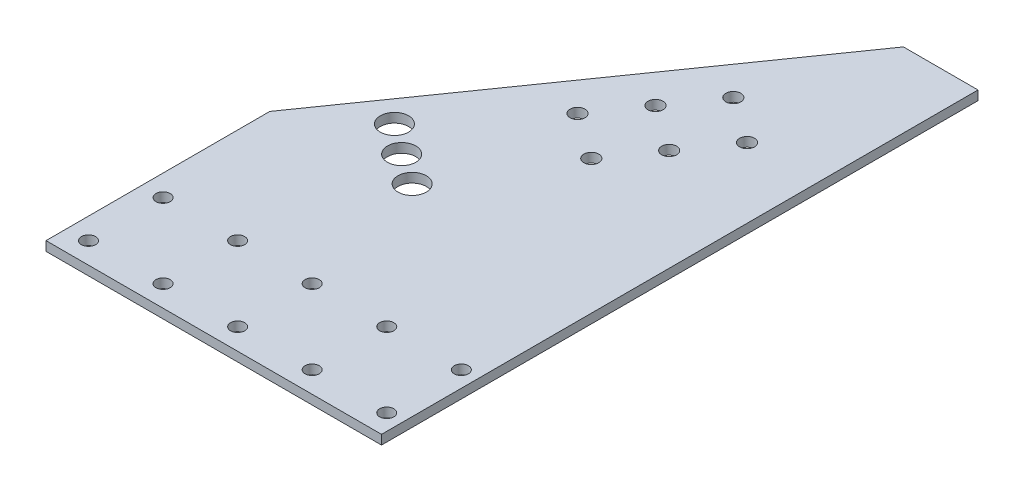
SolidWorks part; units mm, degrees
material "6061-T6 (SS)"
ref_plane "Front Plane" through (0, 0, 0) normal (0, 0, 1) x (1, 0, 0)
ref_plane "Top Plane" through (0, 0, 0) normal (0, 1, 0) x (1, 0, 0)
ref_plane "Right Plane" through (0, 0, 0) normal (1, 0, 0) x (0, 0, -1)
sketch "Sketch1" plane through (0, 0, 0) normal (0, 1, 0) x (1, 0, 0)
  line L5 (0, 0) -> (114.3, 0)
  line L6 (0, 0) -> (0, 203.2)
  line L7 (0, 203.2) -> (114.3, 203.2)
  line L8 (114.3, 0) -> (114.3, 203.2)
  dimension "D1" = 203.2
  dimension "D2" = 114.3
extrude "Boss-Extrude1" add sketch "Sketch1" along normal blind 3.175
sketch "Sketch2" plane through (0, 3.175, 0) normal (0, 1, 0) x (1, 0, 0)
  line L0 (0, 0) -> (114.3, 0) construction
  line L1 (0, 203.2) -> (0, 0) construction
  line L2 (114.3, 0) -> (114.3, 203.2) construction
  line L5 (-1.7463, 0) -> (1.7463, 0) construction
  circle A0 centre (7.239, 7.239) radius 2.413
  circle A2 centre (7.239, 32.639) radius 2.413
  circle A3 centre (32.639, 32.639) radius 2.413
  circle A4 centre (58.039, 32.639) radius 2.413
  circle A5 centre (83.439, 32.639) radius 2.413
  circle A6 centre (108.839, 32.639) radius 2.413
  circle A7 centre (32.639, 7.239) radius 2.413
  circle A8 centre (58.039, 7.239) radius 2.413
  circle A9 centre (83.439, 7.239) radius 2.413
  circle A10 centre (108.839, 7.239) radius 2.413
  dimension "D1" = 4.826
  dimension "D2" = 7.239
  dimension "D3" = 7.239
  dimension "D6" = 25.4
  dimension "D7" = 7.239
  dimension "D8" = 5.461
  dimension "D4" = 2
  dimension "D5" = 5
extrude "Cut-Extrude1" cut sketch "Sketch2" against normal through all
sketch "Sketch5" plane through (0, 0, 0) normal (0, -1, 0) x (-1, 0, 0)
  line L0 (-88.9, 203.2) -> (0, 76.2376)
  line L1 (-114.3, 203.2) -> (0, 203.2) construction
  line L3 (0, 76.2376) -> (0, 203.2)
  line L4 (0, 203.2) -> (-88.9, 203.2)
  dimension "D1" = 55
  dimension "D2" = 88.9
extrude "Cut-Extrude4" cut sketch "Sketch5" against normal through all
sketch "Sketch3" plane through (0, 3.175, 0) normal (0, 1, 0) x (1, 0, 0)
  line L0 (90.481, 148.3438) -> (68.6278, 117.1341) construction
  line L1 (88.9, 203.2) -> (0, 76.2376) construction
  line L2 (114.3, 0) -> (114.3, 203.2) construction
  line L3 (90.481, 148.3438) -> (70.7879, 162.1331) construction
  circle A0 centre (90.481, 148.3438) radius 2.5527
  circle A1 centre (74.8762, 159.2704) radius 2.5527
  circle A3 centre (63.9496, 143.6655) radius 2.5527
  circle A4 centre (79.5544, 132.7389) radius 2.5527
  circle A6 centre (68.6278, 117.1341) radius 2.5527
  circle A7 centre (53.0229, 128.0607) radius 2.5527
  dimension "D1" = 5.1054
  dimension "D2" = 32.7594
  dimension "D4" = 19.05
  dimension "D5" = 23.819
  dimension "D6" = 5.1054
  dimension "D7" = 19.05
  dimension "D9" = 19.05
  dimension "D3" = 3
  dimension "D8" = 3
extrude "Cut-Extrude2" cut sketch "Sketch3" against normal through all
sketch "Sketch6" plane through (0, 3.175, 0) normal (0, 1, 0) x (1, 0, 0)
  line L0 (0, 0) -> (114.3, 0) construction
  line L2 (0, 76.2376) -> (0, 0) construction
  circle A0 centre (24.9267, 93.7768) radius 4.826
  circle A4 centre (35.0484, 86.106) radius 4.826
  circle A5 centre (45.6386, 79.0962) radius 4.826
  circle A6 centre (68.6278, 117.1341) radius 2.5527 construction
  circle A7 centre (68.5706, 117.1741) radius 2.5527 construction
  dimension "D1" = 9.652
  dimension "D2" = 24.9267
  dimension "D3" = 9.652
  dimension "D4" = 9.652
  dimension "D5" = 12.7
  dimension "D6" = 12.7
  dimension "D7" = 45.72
  dimension "D8" = 44.45
  dimension "D9" = 86.106
extrude "Cut-Extrude5" cut sketch "Sketch6" against normal through all
